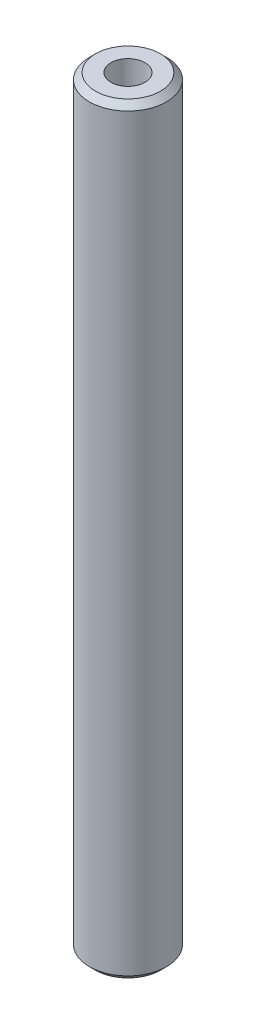
SolidWorks part; units mm, degrees
ref_plane "Front Plane" through (0, 0, 0) normal (0, 0, 1) x (1, 0, 0)
ref_plane "Top Plane" through (0, 0, 0) normal (0, 1, 0) x (1, 0, 0)
ref_plane "Right Plane" through (0, 0, 0) normal (1, 0, 0) x (0, 0, -1)
sketch "Sketch1" plane through (0, 0, 0) normal (0, 1, 0) x (1, 0, 0)
  circle A0 centre (0, 0) radius 5
  dimension "SHAFT_OD" = 10
extrude "Boss-Extrude1" add sketch "Sketch1" along normal blind 98.6365
sketch "Sketch2" plane through (0, 0, 0) normal (0, 1, 0) x (1, 0, 0)
  circle A0 centre (0, 0) radius 2.2074
  dimension "BORE_D" = 4.4147
extrude "Cut-Extrude1" cut sketch "Sketch2" along normal through all
chamfer "Chamfer1" distance 0.7958 angle 45 2 edges at (0, 98.6365, 5) (0, 0, 5)
